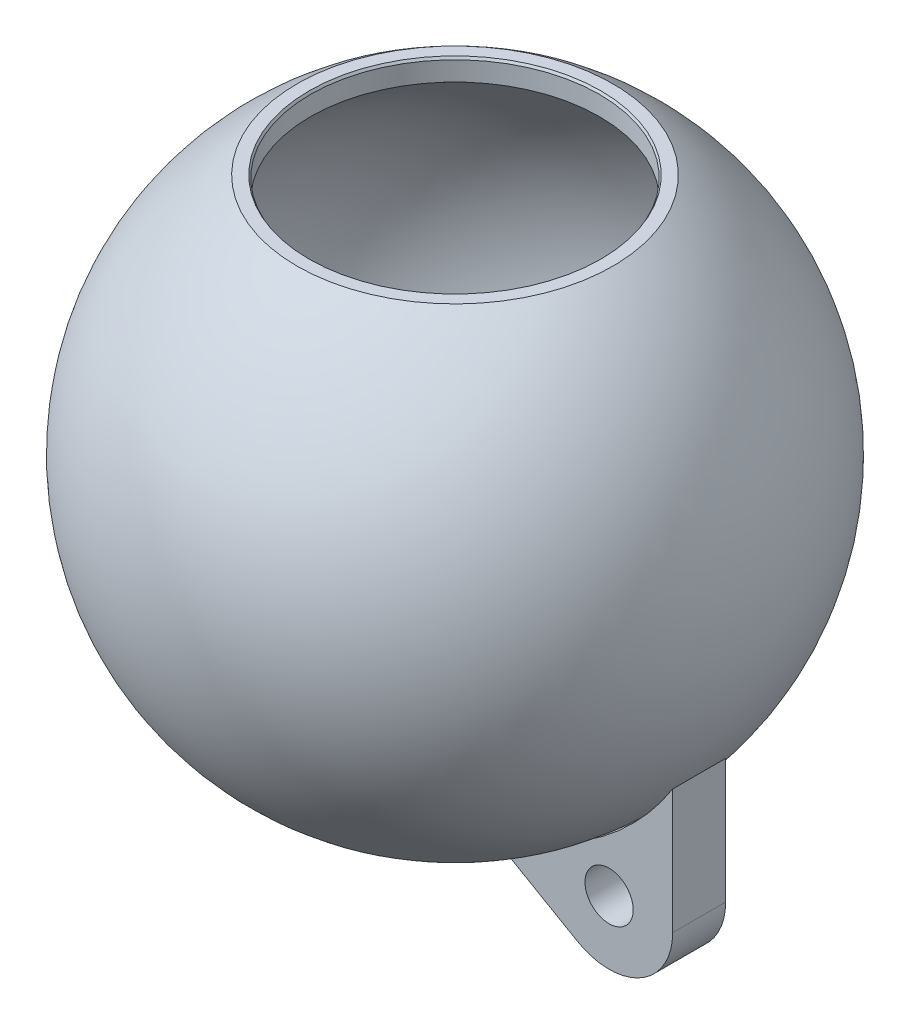
SolidWorks part; units mm, degrees
ref_plane "Front Plane" through (0, 0, 0) normal (0, 0, 1) x (1, 0, 0)
ref_plane "Top Plane" through (0, 0, 0) normal (0, 1, 0) x (1, 0, 0)
ref_plane "Right Plane" through (0, 0, 0) normal (1, 0, 0) x (0, 0, -1)
sketch "Sketch1" plane through (0, 0, 0) normal (0, 1, 0) x (1, 0, 0)
  line L0 (0, -152.4) -> (0, 152.4)
  arc A0 (0, 152.4) -> (0, -152.4) centre (0, 0) ccw
revolve "Revolve3" add sketch "Sketch1" angle 360 about L0
shell "Shell1" thickness 13.462
sketch "Sketch2" plane through (0, 0, 0) normal (0, 1, 0) x (1, 0, 0)
  circle A0 centre (0, 0) radius 76.2
  dimension "D1" = 152.4
extrude "Cut-Extrude1" cut sketch "Sketch2" along normal blind 152.4
sketch "Sketch3" plane through (0, 0, 0) normal (0, 0, 1) x (1, 0, 0)
  line L0 (-128.778, -81.4984) -> (-128.778, -147.1173)
  line L1 (-78.486, -176.1534) -> (-31.6052, -149.0868)
  line L2 (0, 148.9663) -> (0, -195.2598) construction
  line L3 (78.486, -176.1534) -> (31.6052, -149.0868)
  line L4 (128.778, -81.4984) -> (128.778, -147.1173)
  circle A0 centre (0, 0) radius 152.4 construction
  arc A1 (-31.6052, -149.0868) -> (-128.778, -81.4984) centre (0, 0) cw
  circle A2 centre (-95.25, -147.1173) radius 12.7
  arc A3 (-128.778, -147.1173) -> (-78.486, -176.1534) centre (-95.25, -147.1173) ccw
  arc A4 (128.778, -147.1173) -> (78.486, -176.1534) centre (95.25, -147.1173) cw
  circle A5 centre (95.25, -147.1173) radius 12.7
  arc A6 (31.6052, -149.0868) -> (128.778, -81.4984) centre (0, 0) ccw
  point P0 (-128.778, -81.4984)
  point P1 (-128.778, -205.1895)
  point P5 (-31.6052, -149.0868)
  point P6 (-128.778, -205.1895)
  point P8 (-87.0215, -125.112)
  point P22 (-128.778, -205.1895)
  point P23 (128.778, -205.1895)
  point P25 (-112.014, -176.1534)
  dimension "D1" = 33.528
  dimension "D2" = 60
  dimension "D3" = 95.25
  dimension "D4" = 25.4
  dimension "D5" = 175.26
extrude "Boss-Extrude1" add sketch "Sketch3" along normal blind 13.97 and the other way blind 13.97 separate body
ref_plane "Plane1" through (0, 116.178, 0) normal (0, 1, 0) x (1, 0, 0)
ref_plane "Plane2" through (0, 127.608, 0) normal (0, 1, 0) x (1, 0, 0)
sketch "Sketch4" plane through (0, 127.608, 0) normal (0, 1, 0) x (1, 0, 0)
  circle A0 centre (0, 0) radius 76.2 construction
  circle A1 centre (0, 0) radius 76.2
extrude "Cut-Extrude-Thin1" cut sketch "Sketch4" along normal blind 7.62 flip side to cut thin thin type one direction wall 12.7
chamfer "Chamfer1" distance 1.27 angle 30 1 edges at (0, 127.608, 76.2) first distance on face at (0, 116.178, -76.2)
